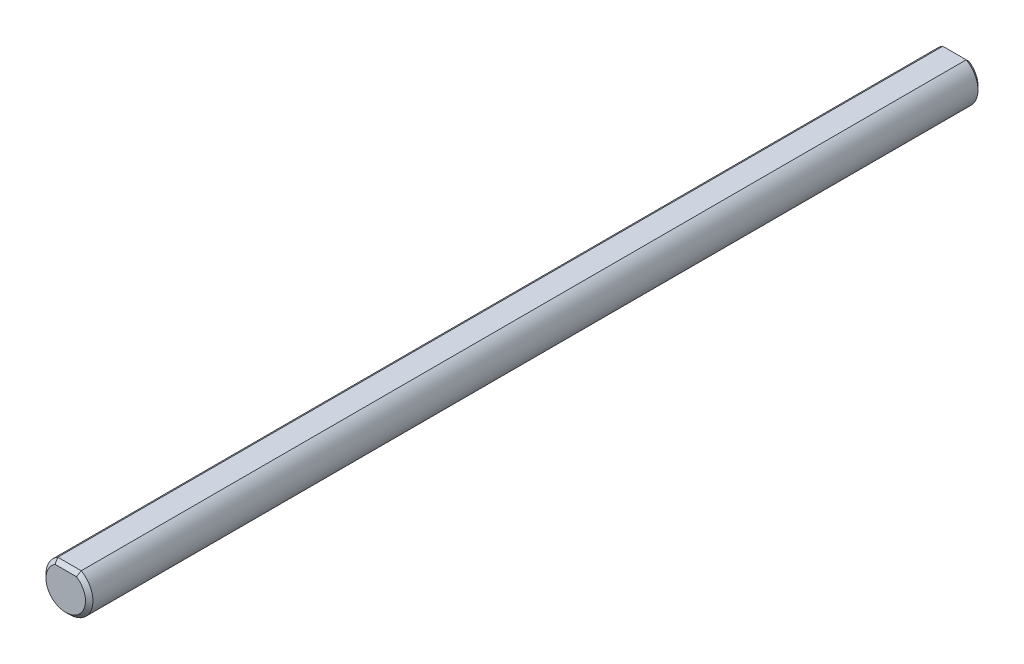
SolidWorks part; units mm, degrees
ref_plane "Front Plane" through (0, 0, 0) normal (0, 0, 1) x (1, 0, 0)
ref_plane "Top Plane" through (0, 0, 0) normal (0, 1, 0) x (1, 0, 0)
ref_plane "Right Plane" through (0, 0, 0) normal (1, 0, 0) x (0, 0, -1)
sketch "Sketch1" plane through (0, 0, 0) normal (0, 0, 1) x (1, 0, 0)
  line L0 (-1.5875, 2.7496) -> (1.5875, 2.7496)
  arc A0 (-1.5875, 2.7496) -> (1.5875, 2.7496) centre (0, 0) ccw
  dimension "D1" = 6.35
  dimension "D2" = 3.175
extrude "Boss-Extrude1" add sketch "Sketch1" along normal blind 120.65
chamfer "Chamfer1" distance 0.508 angle 45 4 edges at (0, 2.7496, 120.65) (0, -3.175, 120.65) (0, 2.7496, 0) (0, -3.175, 0)
